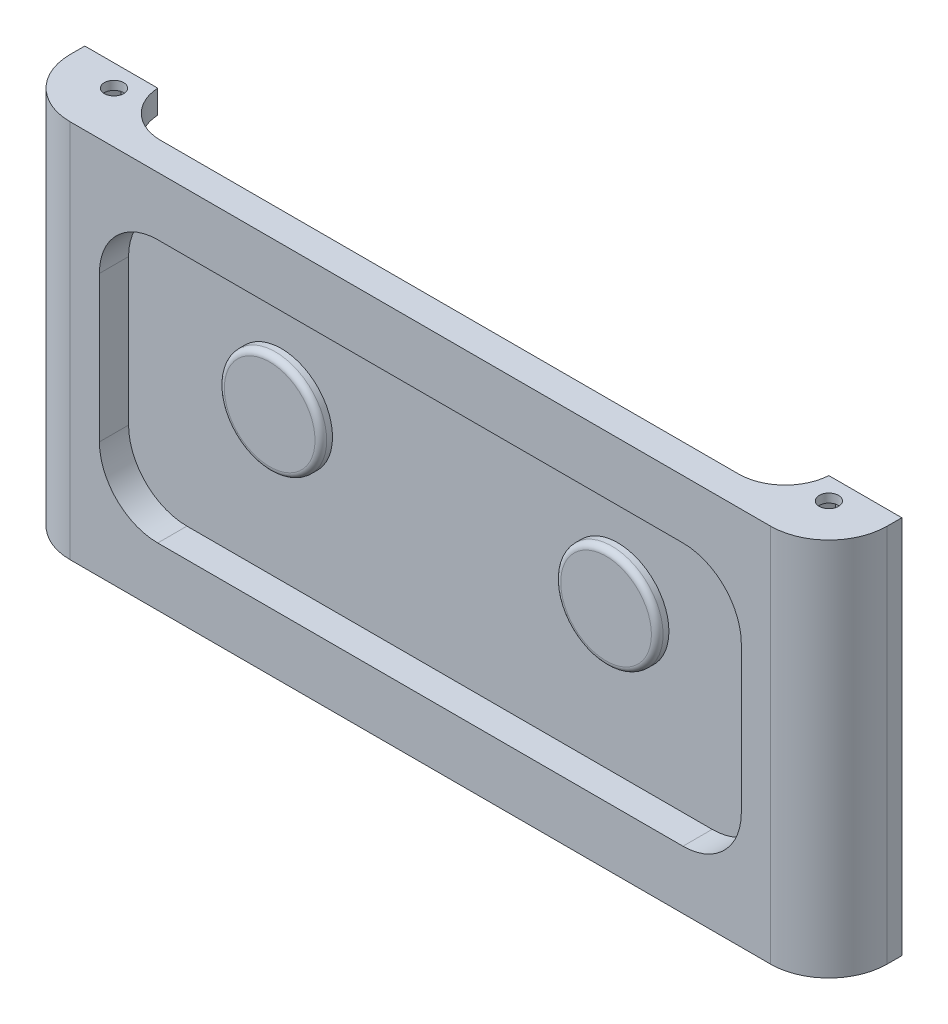
SolidWorks part; units mm, degrees
ref_plane "Front Plane" through (0, 0, 0) normal (0, 0, 1) x (1, 0, 0)
ref_plane "Top Plane" through (0, 0, 0) normal (0, 1, 0) x (1, 0, 0)
ref_plane "Right Plane" through (0, 0, 0) normal (1, 0, 0) x (0, 0, -1)
sketch "Sketch1" plane through (0, 0, 0) normal (0, 0, 1) x (1, 0, 0)
  line L1 (0, 0) -> (140, 0)
  line L2 (0, 0) -> (0, 65)
  line L3 (0, 65) -> (140, 65)
  line L4 (140, 0) -> (140, 65)
  point P6 (65.6215, 39.2286)
  point P12 (70, 45)
  dimension "D1" = 140
  dimension "D2" = 65
extrude "Boss-Extrude1" add sketch "Sketch1" along normal blind 12.5
sketch "Sketch4" plane through (0, 65, 0) normal (0, 1, 0) x (1, 0, 0)
  line L6 (5, 0) -> (135, 0)
  line L9 (135, 0) -> (135, -7.5)
  line L10 (5, -7.5) -> (5, 0)
  line L11 (135, -7.5) -> (5, -7.5)
  line L12 (135, 0) -> (135, -7.5)
  line L13 (5, -7.5) -> (5, 0)
  line L14 (135, -7.5) -> (5, -7.5)
  dimension "D1" = 5
extrude "Cut-Extrude3" cut sketch "Sketch4" against normal through all
sketch "Sketch2" plane through (0, 0, 12.5) normal (0, 0, 1) x (1, 0, 0)
  line L0 (70, 65) -> (70, 0) construction
  line L1 (140, 65) -> (0, 65) construction
  line L2 (0, 0) -> (140, 0) construction
  line L3 (140, 0) -> (140, 65) construction
  line L4 (15, 55) -> (125, 55)
  line L5 (15, 55) -> (15, 10)
  line L6 (15, 10) -> (125, 10)
  line L7 (125, 55) -> (125, 10)
  line L8 (15, 55) -> (125, 10) construction
  line L9 (15, 10) -> (125, 55) construction
  point P6 (70, 32.5)
  dimension "D1" = 15
  dimension "D2" = 10
extrude "Cut-Extrude1" cut sketch "Sketch2" against normal through all
fillet "Fillet1" radius 10 4 edges at (15, 10, 10) (15, 55, 10) (125, 10, 10) (125, 55, 10)
fillet "Fillet2" radius 10 2 edges at (140, 32.5, 12.5) (0, 32.5, 12.5)
sketch "Sketch5" plane through (0, 0, 0) normal (0, -1, 0) x (1, 0, 0)
  line L0 (0, 0) -> (5, 0) construction
  line L1 (5, 7.5) -> (12.5, 7.5)
  line L2 (5, 7.5) -> (5, 0)
  line L3 (5, 0) -> (12.5, 0)
  line L4 (12.5, 7.5) -> (12.5, 0)
  line L5 (135, 7.5) -> (127.5, 7.5)
  line L6 (135, 7.5) -> (135, 0)
  line L7 (135, 0) -> (127.5, 0)
  line L8 (127.5, 7.5) -> (127.5, 0)
extrude "Boss-Extrude2" add sketch "Sketch5" against normal blind 4
sketch "Sketch6" plane through (0, 4, 0) normal (0, 1, 0) x (1, 0, 0)
  line L0 (8.75, 0) -> (8.75, -7.5) construction
  line L1 (11.9254, -3.75) -> (10.3377, -1)
  line L2 (10.3377, -1) -> (7.1623, -1)
  line L3 (7.1623, -1) -> (5.5746, -3.75)
  line L4 (5.5746, -3.75) -> (7.1623, -6.5)
  line L5 (7.1623, -6.5) -> (10.3377, -6.5)
  line L6 (10.3377, -6.5) -> (11.9254, -3.75)
  line L7 (5, 0) -> (12.5, 0) construction
  line L8 (12.5, -7.5) -> (5, -7.5) construction
  line L9 (70, -12.5) -> (70, 1.5241) construction
  line L10 (130, -12.5) -> (10, -12.5) construction
  line L11 (134.4254, -3.75) -> (132.8377, -6.5)
  line L12 (132.8377, -6.5) -> (129.6623, -6.5)
  line L13 (129.6623, -6.5) -> (128.0746, -3.75)
  line L14 (128.0746, -3.75) -> (129.6623, -1)
  line L15 (129.6623, -1) -> (132.8377, -1)
  line L16 (132.8377, -1) -> (134.4254, -3.75)
  circle A0 centre (8.75, -3.75) radius 2.75 construction
  circle A1 centre (8.75, -3.75) radius 1.65
  circle A2 centre (131.25, -3.75) radius 1.65
  point P21 (10.0949, -1.4206)
  dimension "D1" = 3.3
  dimension "D2" = 5.5
extrude "Cut-Extrude5" cut sketch "Sketch6<2>" against normal through all contours A1 | A2 region at (8.75, 4, 3.75) region at (131.25, 4, 3.75)
sketch "Sketch6<2>" plane through (0, 4, 0) normal (0, 1, 0) x (1, 0, 0) same geometry as "Sketch6"
extrude "Cut-Extrude4" cut sketch "Sketch6" against normal blind 2.5
fillet "Fillet3" radius 8 2 edges at (127.5, 2, 7.5) (12.5, 2, 7.5)
ref_plane "Plane1" through (0, 32.5, 0) normal (0, 1, 0) x (1, 0, 0)
mirror "Mirror1" about plane through (0, 32.5, 0) normal (0, 1, 0) of "Cut-Extrude5", "Cut-Extrude4", "Boss-Extrude2", "Fillet3"
sketch "Sketch7" plane through (0, 0, 7.5) normal (0, 0, -1) x (-1, 0, 0)
  line L1 (-135, 61) -> (-5, 61)
  line L2 (-135, 61) -> (-135, 4)
  line L3 (-135, 4) -> (-5, 4)
  line L4 (-5, 61) -> (-5, 4)
extrude "Boss-Extrude3" add sketch "Sketch7" along normal blind 1 separate body
sketch "Sketch8" plane through (0, 0, 7.5) normal (0, 0, 1) x (1, 0, 0)
  line L0 (70, 55) -> (70, 24.7719) construction
  line L1 (115, 55) -> (25, 55) construction
  line L2 (25, 10) -> (115, 10) construction
  line L3 (41.1771, 35.6804) -> (98.8229, 35.6804) construction
  line L5 (70, 19.7719) -> (70, 10) construction
  circle A0 centre (41.1771, 35.6804) radius 8.769
  circle A1 centre (98.8229, 35.6804) radius 8.769
  point P11 (70, 35.6804)
  point P12 (98.8229, 49.731)
extrude "Boss-Extrude4" add sketch "Sketch8" along normal blind 2 separate body contours A0 | A1 region at (41.1771, 35.6804, 7.5) region at (98.8229, 35.6804, 7.5)
sketch "Sketch9" plane through (0, 0, 6.5) normal (0, 0, -1) x (-1, 0, 0)
  line L0 (-19, 0) -> (-19, 42.7) construction
  line L1 (-20.4844, 0) -> (-119.5156, 0) construction
  line L2 (0, 0) -> (-19, 0) construction
  line L3 (-70, 65) -> (-70, 0) construction
  line L4 (-20.4844, 65) -> (-119.5156, 65) construction
  circle A0 centre (-19, 42.7) radius 8.4
  circle A1 centre (-121, 42.7) radius 8.4
  point P11 (-70, 0)
  dimension "D3" = 16.8
  dimension "D1" = 19
  dimension "D2" = 42.7
extrude "Boss-Extrude6" add sketch "Sketch9" along normal blind 10 separate body
combine bodies "Combine1" operation type add bodies to combine 116 110 117
chamfer "Chamfer1" distance 3 angle 45 2 edges at (10.6, 42.7, 6.5) (112.6, 42.7, 6.5)
fillet "Fillet5" radius 1 2 edges at (10.6, 42.7, -3.5) (129.4, 42.7, -3.5)
fillet "Fillet6" radius 1 1 edges at (107.5919, 35.6804, 9.5)
fillet "Fillet7" radius 1 1 edges at (49.9461, 35.6804, 9.5)
